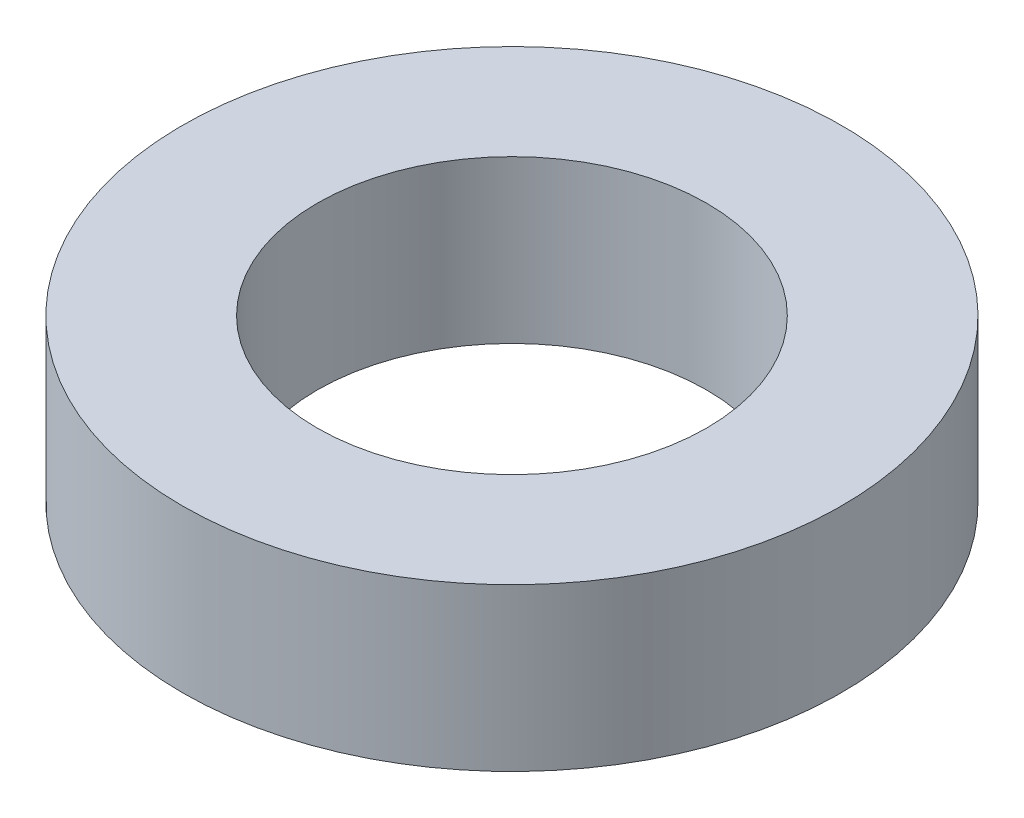
SolidWorks part; units mm, degrees
ref_plane "Front Plane" through (0, 0, 0) normal (0, 0, 1) x (1, 0, 0)
ref_plane "Top Plane" through (0, 0, 0) normal (0, 1, 0) x (1, 0, 0)
ref_plane "Right Plane" through (0, 0, 0) normal (1, 0, 0) x (0, 0, -1)
sketch "Sketch1" plane through (0, 0, 0) normal (0, 1, 0) x (1, 0, 0)
  circle A0 centre (0, 0) radius 55
  dimension "FLANGE_OD" = 110
extrude "Boss-Extrude1" add sketch "Sketch1" along normal blind 27
sketch "Sketch2" plane through (0, 0, 0) normal (0, 1, 0) x (1, 0, 0)
  circle A0 centre (0, 0) radius 32.5
  dimension "BORE_D" = 65
extrude "Cut-Extrude1" cut sketch "Sketch2" along normal through all
sketch "Sketch3" plane through (0, 27, 0) normal (0, 1, 0) x (1, 0, 0)
  circle A0 centre (0, 0) radius 24.7998 construction
  circle A1 centre (-24.7998, 0) radius 3.33
  dimension "BOLT_D" = 6.6599
  dimension "BOLT_PCD" = 49.5997
extrude "Cut-Extrude2" cut sketch "Sketch3" against normal blind 22.825 rebuild error yes
pattern_circular "CirPattern1" count 6 over 360 rebuild error yes
